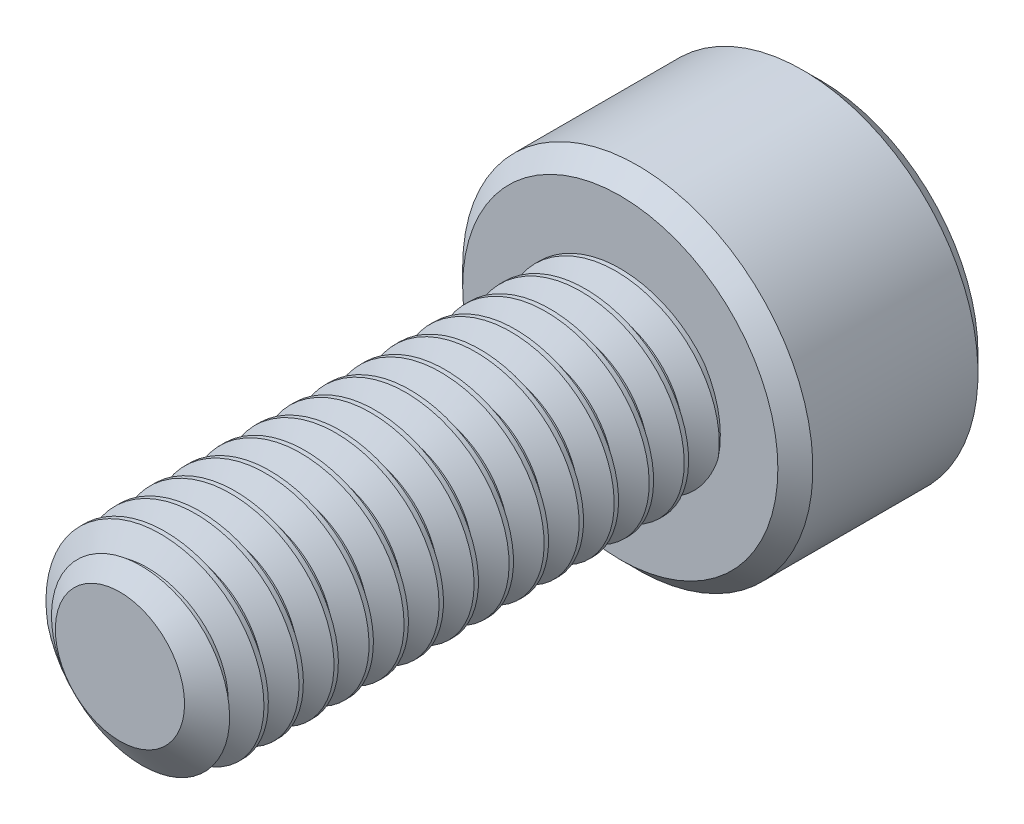
SolidWorks part; units mm, degrees
other "DetailItem1"
ref_plane "Front Plane" through (0, 0, 0) normal (0, 0, 1) x (1, 0, 0)
ref_plane "Top Plane" through (0, 0, 0) normal (0, 1, 0) x (1, 0, 0)
ref_plane "Right Plane" through (0, 0, 0) normal (1, 0, 0) x (0, 0, -1)
sketch "Sketch1" plane through (0, 0, 0) normal (0, 0, 1) x (1, 0, 0)
  circle A0 centre (0, 0) radius 2
  dimension "OD" = 4
extrude "Extrude1" add sketch "Sketch1" against normal blind 10
sketch "Sketch2" plane through (0, 0, 0) normal (0, 0, 1) x (1, 0, 0)
  circle A0 centre (0, 0) radius 2 construction
  circle A1 centre (0, 0) radius 2
curve "Helix/Spiral1" pitch 0.7 height 10.7 radius 2 centre (0, 0, 0) axis (0, 0, -1) start towards (0, 1, 0) parameters "pitch"=0.7
sketch "Sketch3" plane through (0, 0, 0) normal (1, 0, 0) x (0, 0, -1)
  line L0 (-0.6125, 2) -> (-0.35, 1.5453)
  line L1 (-0.35, 1.5453) -> (-0.2625, 1.5453)
  line L2 (-0.2625, 1.5453) -> (0, 2)
  line L3 (-0.6125, 2) -> (0, 2)
  line L4 (-0.3062, 2) -> (-0.3062, 1.5453) construction
  line L5 (-0.4812, 1.7727) -> (-0.1312, 1.7727) construction
  line L6 (0, 2) -> (0, -2) construction
  dimension "D1" = 0.0875
  dimension "D2" = 0.35
  dimension "D3" = 60
sweep "Cut-Sweep1" cut profiles "Sketch3" path "Helix/Spiral1"
sketch "Sketch4" plane through (0, 0, 0) normal (1, 0, 0) x (0, 0, -1)
  line L0 (0.4962, 2) -> (0, 1.2913)
  line L1 (0, 1.2913) -> (0, 2)
  line L2 (0.4962, 2) -> (0, 2)
  line L3 (-0.6125, 2) -> (0, 2) construction
  line L4 (0, 0) -> (7.0209, 0) construction
  dimension "D1" = 55
  dimension "D2" = 0.254
revolve "Cut-Revolve1" cut sketch "Sketch4" angle 360 about L4
sketch "Sketch6" plane through (0, 0, -10) normal (0, 0, -1) x (-1, 0, 0)
  circle A0 centre (0, 0) radius 3.5
  dimension "head dia" = 7
extrude "Extrude2" add sketch "Sketch6" along normal blind 4
sketch "Sketch7" plane through (0, 0, -14) normal (0, 0, -1) x (-1, 0, 0)
  line L1 (0, 1.7321) -> (-1.5, 0.866)
  line L2 (-1.5, 0.866) -> (-1.5, -0.866)
  line L3 (-1.5, -0.866) -> (0, -1.7321)
  line L4 (0, -1.7321) -> (1.5, -0.866)
  line L5 (1.5, -0.866) -> (1.5, 0.866)
  line L6 (1.5, 0.866) -> (0, 1.7321)
  circle A0 centre (0, 0) radius 1.5 construction
  dimension "hex dia" = 3
extrude "Cut-Extrude1" cut sketch "Sketch7" against normal blind 2.25
sketch "Sketch8" plane through (0, 0, -14) normal (0, 0, -1) x (-1, 0, 0)
  circle A0 centre (0, 0) radius 1.7321
extrude "Cut-Extrude2" cut sketch "Sketch8" against normal through all draft 45
chamfer "Chamfer1" distance 0.35 angle 45 2 edges at (-3.5, 0, -14) (-3.5, 0, -10)
sketch "Sketch10" plane through (0, 0, -10) normal (0, 0, 1) x (1, 0, 0)
  circle A1 centre (0, 0) radius 2
  circle A2 centre (0, 0) radius 2
  dimension "D1" = 0
ref_plane "Plane1" through (0, 0, 0) normal (0, 0, 1) x (1, 0, 0)
extrude "partial thread" [suppressed] add sketch "Sketch10" along normal up to surface (10 mm away) separate body up to plane "Plane1"
chamfer "Chamfer2" [suppressed] distance 0.08 angle 45
combine bodies "Combine1" [suppressed] operation type add bodies to combine 107 108
sketch "Sketch9" plane through (0, 0, 0) normal (1, 0, 0) x (0, 0, -1)
  line L0 (0, 2) -> (0, -2) construction
  line L1 (1.75, 2) -> (1.75, -2) construction
  dimension "D1" = 1.75
  dimension "D4" = 0.635
  dimension "D5" = 0.3302
equation "\"D3@Helix/Spiral1\" = \"screw length@Extrude1\"+\"pitch@Helix/Spiral1\""
equation "\"D1@Sketch3\" = \"pitch@Helix/Spiral1\"*.125"
equation "\"D2@Sketch3\" = \"pitch@Helix/Spiral1\"*.5"
equation "\"D1@Cut-Extrude1\" = \"hex dia@Sketch7\"*.75"
equation "\"D1@Chamfer1\" = \"head dia@Sketch6\"*.05"
equation "\"D1@Sketch9\" = \"pitch@Helix/Spiral1\"*2.5"
equation "\"D1@Chamfer2\"=\"OD@Sketch1\"*.02"
